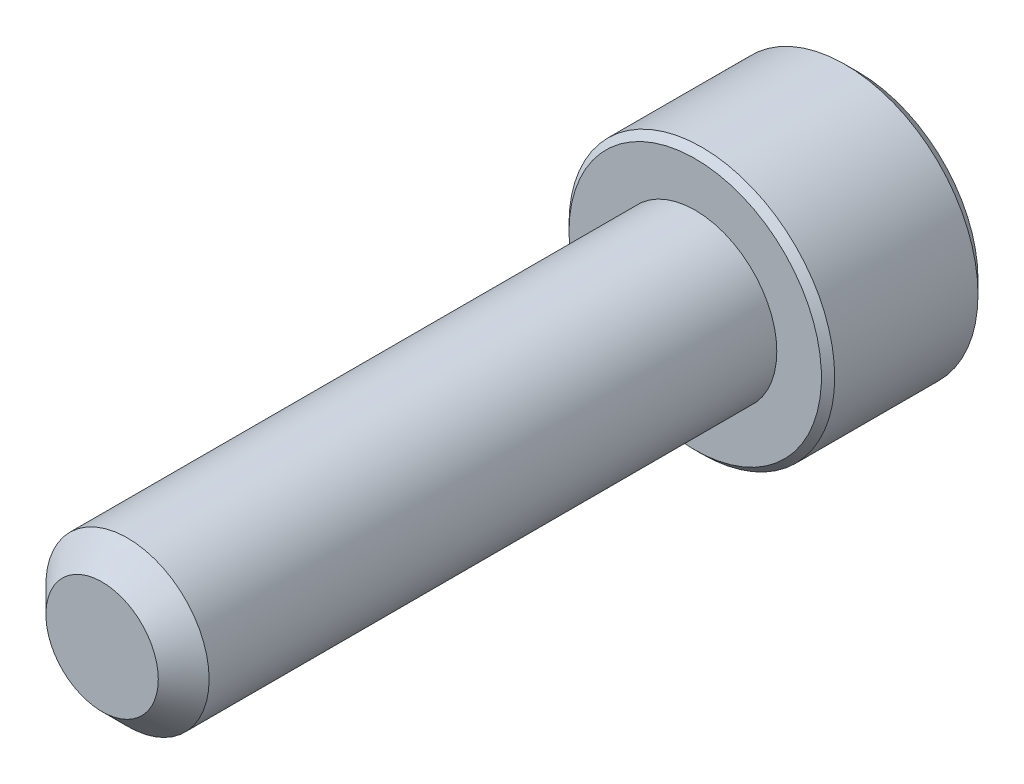
SolidWorks part; units mm, degrees
material "AISI 304"
ref_plane "Front Plane" through (0, 0, 0) normal (0, 0, 1) x (1, 0, 0)
ref_plane "Top Plane" through (0, 0, 0) normal (0, 1, 0) x (1, 0, 0)
ref_plane "Right Plane" through (0, 0, 0) normal (1, 0, 0) x (0, 0, -1)
sketch "Sketch0" plane through (0, 0, 0) normal (1, 0, 0) x (0, 0, -1)
  line L0 (0, 0) -> (7.9375, 0) construction
  point P2 (10.1219, 0)
  point P4 (0, 0)
  dimension "D1" = 7.9375
  dimension "D2" = 2.1844
  dimension "Min Thread" = 0
sketch "Sketch1" plane through (0, 0, 0) normal (0, 0, 1) x (1, 0, 0)
  circle A0 centre (0, 0) radius 1.0922
  dimension "OD" = 2.1844
extrude "Extrude1" add sketch "Sketch1" against normal blind 7.9375
sketch "Sketch2" plane through (0, 0, 0) normal (0, 0, 1) x (1, 0, 0)
  circle A0 centre (0, 0) radius 1.0922 construction
  circle A1 centre (0, 0) radius 1.0922
curve "Helix/Spiral1" [suppressed] pitch 0.4536 height 8.3911 turns 18.5 parameters "pitch"=0.4536
chamfer "Chamfer3" distance 0.3402 angle 45 1 edges at (1.0922, 0, 0)
sketch "Sketch3" plane through (0, 0, 0) normal (1, 0, 0) x (0, 0, -1)
  line L0 (-0.3969, 1.0922) -> (-0.2268, 0.7976)
  line L1 (-0.2268, 0.7976) -> (-0.1701, 0.7976)
  line L2 (-0.1701, 0.7976) -> (0, 1.0922)
  line L3 (-0.3969, 1.0922) -> (0, 1.0922)
  line L4 (-0.1984, 1.0922) -> (-0.1984, 0.7976) construction
  line L5 (-0.3118, 0.9449) -> (-0.085, 0.9449) construction
  line L6 (0, 1.0922) -> (0, -1.0922) construction
  dimension "D1" = 0.0567
  dimension "D2" = 0.2268
  dimension "D3" = 60
sweep "Cut-Sweep1" [suppressed] cut profiles "Sketch3" path "Helix/Spiral1"
sketch "Sketch5" [suppressed] plane through (0, 0, 0) normal (1, 0, 0) x (0, 0, -1)
  line L0 (7.9375, -0.7793) -> (7.9375, 0.8061) construction
  line L1 (7.9375, 1.0922) -> (0, 1.0922)
  line L2 (7.9375, 1.0922) -> (7.9375, 0)
  line L3 (7.9375, 0) -> (-0.3975, 0)
  line L4 (0, 0) -> (7.9375, 0) construction
  line L5 (0, 1.0922) -> (-0.3975, 0)
  line L6 (0, 0) -> (10.4775, 0) construction
  dimension "D1" = 70
  dimension "D3" = 2.54
revolve "partially thread" [suppressed] add sketch "Sketch5" angle 360 about L6
sketch "Sketch6" plane through (0, 0, -7.9375) normal (0, 0, -1) x (-1, 0, 0)
  circle A0 centre (0, 0) radius 1.778
  dimension "head dia" = 3.556
extrude "Extrude2" add sketch "Sketch6" along normal blind 2.1844
sketch "Sketch7" plane through (0, 0, -10.1219) normal (0, 0, -1) x (-1, 0, 0)
  line L1 (0, 1.1457) -> (-0.9922, 0.5728)
  line L2 (-0.9922, 0.5728) -> (-0.9922, -0.5728)
  line L3 (-0.9922, -0.5728) -> (0, -1.1457)
  line L4 (0, -1.1457) -> (0.9922, -0.5728)
  line L5 (0.9922, -0.5728) -> (0.9922, 0.5728)
  line L6 (0.9922, 0.5728) -> (0, 1.1457)
  circle A0 centre (0, 0) radius 0.9922 construction
  dimension "hex dia" = 1.9844
extrude "Cut-Extrude1" cut sketch "Sketch7" against normal blind 1.4883
sketch "Sketch8" plane through (0, 0, -10.1219) normal (0, 0, -1) x (-1, 0, 0)
  circle A0 centre (0, 0) radius 1.1457
extrude "Cut-Extrude2" cut sketch "Sketch8" against normal through all draft 45
chamfer "Chamfer1" distance 0.1778 angle 45 1 edges at (-1.778, 0, -10.1219)
chamfer "Chamfer2" distance 0.0889 angle 45 1 edges at (-1.778, 0, -7.9375)
sketch "Sketch9" plane through (0, 0, 0) normal (1, 0, 0) x (0, 0, -1)
  line L0 (0, 1.0922) -> (0, -1.0922) construction
  line L1 (1.5875, 1.0922) -> (1.5875, -1.0922) construction
  line L2 (10.1219, 1.778) -> (10.1219, -1.778) construction
  line L3 (7.9375, 1.778) -> (7.9375, -1.778) construction
  line L4 (7.9375, 1.6891) -> (7.9375, -1.6891) construction
  line L5 (10.1219, -1.6002) -> (10.1219, 1.6002) construction
  line L6 (7.9375, -1.778) -> (7.9375, 1.778) construction
  line L7 (0, 0.752) -> (0, -0.752) construction
  line L8 (-0.3969, 1.0922) -> (0, 1.0922) construction
  line L9 (1.5875, 0) -> (0, 0) construction
  dimension "D1" = 1.5875
equation "\"D3@Helix/Spiral1\" = \"screw length@Extrude1\"+\"pitch@Helix/Spiral1\""
equation "\"D1@Sketch3\" = \"pitch@Helix/Spiral1\"*.125"
equation "\"D2@Sketch3\" = \"pitch@Helix/Spiral1\"*.5"
equation "\"D1@Cut-Extrude1\" = \"hex dia@Sketch7\"*.75"
equation "\"D1@Chamfer1\" = \"head dia@Sketch6\"*.05"
equation "\"D1@Sketch9\" = \"pitch@Helix/Spiral1\"*3.50"
equation "\"D1@Chamfer2\" = \"D1@Chamfer1\"/2"
equation "\"D1@Chamfer3\" = \"pitch@Helix/Spiral1\"*.750"
equation "\"D1@Sketch0\" = \"screw length@Extrude1\""
equation "\"D2@Sketch0\" = \"head depth@Extrude2\""
